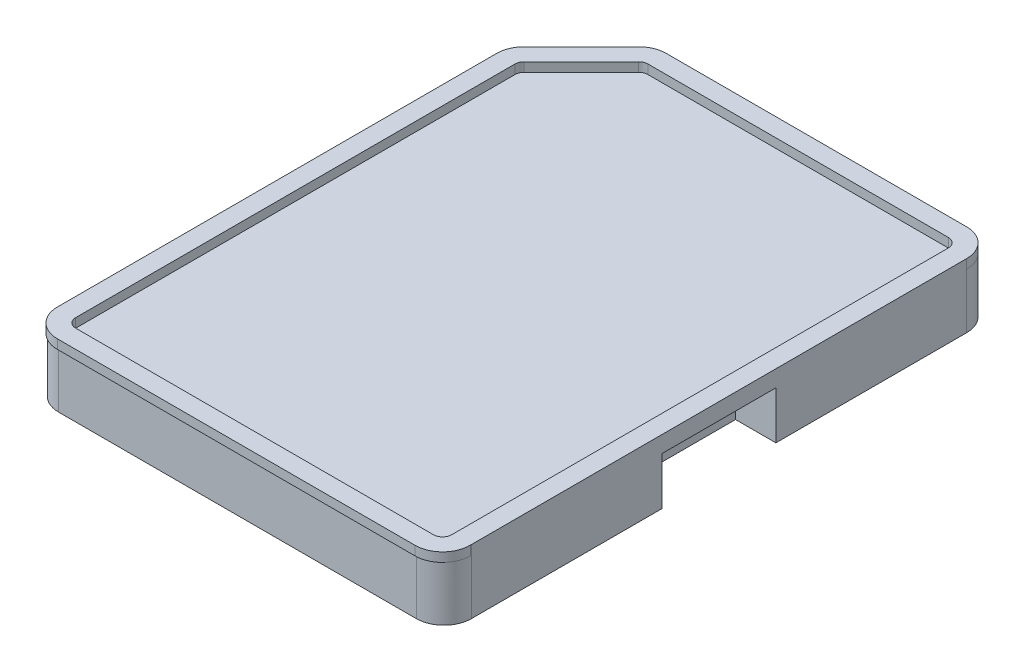
SolidWorks part; units mm, degrees
ref_plane "Спереди" through (0, 0, 0) normal (0, 0, 1) x (1, 0, 0)
ref_plane "Сверху" through (0, 0, 0) normal (0, 1, 0) x (1, 0, 0)
ref_plane "Справа" through (0, 0, 0) normal (1, 0, 0) x (0, 0, -1)
sketch "surface_sketch" plane through (0, 0, 0) normal (0, 1, 0) x (1, 0, 0)
  line L2 (-12.4, -15) -> (10.1, -15)
  line L3 (10.1, -15) -> (10.1, 15)
  line L4 (0.1, 0) -> (0.1, -15) construction
  line L5 (0.1, 0) -> (10.1, 0) construction
  line L7 (-8.4, 15) -> (10.1, 15)
  line L8 (-12.4, 11) -> (-12.4, -15)
  line L9 (-3.65, -15) -> (-3.65, -7.5) construction
  line L10 (-3.65, -7.5) -> (0.1, -7.5) construction
  line L11 (-3.65, -7.5) -> (-3.65, 0) construction
  line L12 (-3.65, 0) -> (-3.65, 7.5) construction
  line L13 (-1.3, 7.5) -> (-6, 7.5)
  line L14 (-6, 0) -> (-1.3, 0)
  line L15 (-6, -7.5) -> (-1.3, -7.5)
  line L16 (6.2, -7.5) -> (1.5, -7.5)
  line L17 (6.2, 0) -> (1.5, 0) construction
  line L18 (3.85, 7.5) -> (1.5, 7.5)
  line L19 (0, 0) -> (0.1, 0) construction
  line L20 (3.85, 7.5) -> (6.2, 7.5)
  line L21 (-8.4, 15) -> (-12.4, 11)
  line L22 (-12.4, 11) -> (-12.4, 15) construction
  line L23 (-12.4, 15) -> (-8.4, 15) construction
  circle A0 centre (-3.65, 7.5) radius 2.35
  circle A1 centre (-3.65, 0) radius 2.35
  circle A2 centre (-3.65, -7.5) radius 2.35
  circle A3 centre (3.85, -7.5) radius 2.35
  circle A4 centre (3.85, 0) radius 2.35
  circle A5 centre (3.85, 7.5) radius 2.35
  dimension "D9" = 4.7
  dimension "D10" = 4.7
  dimension "D11" = 4.7
  dimension "D1" = 22.5
  dimension "D2" = 30
  dimension "D5" = 7.5
  dimension "D6" = 3.75
  dimension "D7" = 7.5
  dimension "D8" = 7.5
  dimension "D3" = 10
  dimension "D4" = 0.1
  dimension "D12" = 4
  dimension "D13" = 4
extrude "body" add sketch "surface_sketch" against normal blind 3
ref_plane "midplane" through (-1.15, 0, 0) normal (1, 0, 0) x (0, 0, -1)
sketch "magnet_cutout_sketch" plane through (0, -3, 0) normal (0, -1, 0) x (1, 0, 0)
  line L0 (10.1, 15) -> (10.1, -15) construction
  line L1 (7.9, 3.1) -> (10.1, 3.1)
  line L2 (7.9, 3.1) -> (7.9, -3.1)
  line L3 (7.9, -3.1) -> (10.1, -3.1)
  line L4 (10.1, 3.1) -> (10.1, -3.1)
  line L5 (9, -3.1) -> (9, 3.1) construction
  line L6 (7.9, 0) -> (10.1, 0) construction
  line L7 (-1.15, 15) -> (-1.15, -15) construction
  line L8 (-12.4, 15) -> (10.1, 15) construction
  line L9 (-8.4, -15) -> (10.1, -15) construction
  line L11 (-1.15, 0) -> (10.1, 0) construction
  line L12 (10.1, 15) -> (10.1, -15) construction
  point P0 (9, 0)
  dimension "D1" = 2.2
  dimension "D2" = 6.2
extrude "magnet_cutout" cut sketch "magnet_cutout_sketch" against normal blind 2.6
mirror "magnet_cutout_mirror" about plane through (-1.15, 0, 0) normal (1, 0, 0) of "magnet_cutout"
sketch "border_sketch" plane through (0, 0, 0) normal (0, 1, 0) x (1, 0, 0)
  line L0 (-12.4, -13.5714) -> (-12.4, 10.3787)
  line L1 (10.1, -13.5714) -> (10.1, 13.5)
  line L2 (8.6, 15) -> (-7.7787, 15)
  line L4 (-1.15, 15) -> (-1.15, -15.0714) construction
  line L5 (-12.4, -0.0357) -> (10.1, -0.0357) construction
  line L6 (-8.4, 15) -> (10.1, 15) construction
  line L7 (10.1, -15) -> (10.1, 15) construction
  line L8 (-10.9, -15.0714) -> (8.6, -15.0714)
  line L9 (-8.8393, 14.5607) -> (-11.9607, 11.4393)
  arc A2 (10.1, 13.5) -> (8.6, 15) centre (8.6, 13.5) ccw
  arc A4 (10.1, -13.5714) -> (8.6, -15.0714) centre (8.6, -13.5714) cw
  arc A5 (-12.4, -13.5714) -> (-10.9, -15.0714) centre (-10.9, -13.5714) ccw
  arc A6 (-12.4, 10.3787) -> (-11.9607, 11.4393) centre (-10.9, 10.3787) cw
  arc A7 (-8.8393, 14.5607) -> (-7.7787, 15) centre (-7.7787, 13.5) cw
  point P6 (10.1, -15.0714)
  point P19 (-12.4, 11)
  point P27 (-8.4, 15)
  dimension "D1" = 1.5
  dimension "D2" = 1.5
extrude "border" add sketch "border_sketch" along normal blind 0.5 thin contours L0 L2 A2 L1
fillet "Скругление1" radius 1.5 5 edges at (10.1, -1.5, 15) (10.1, -1.5, -15) (-12.4, -1.5, 15) (-8.4, -1.5, -15) (-12.4, -1.5, -11)
equation "\"hole_diam\"= 4.7мм"
equation "\"cell_width\"= \"cell_pace\""
equation "\"cell_pace\"= 22.5мм'distance between neighbouring cells"
equation "\"holes_horisontal_dist\"= 7.5"
equation "\"holes_vertical_dist\"= \"holes_horisontal_dist\""
equation "\"cell_length\"= \"holes_vertical_dist\" * 4"
equation "\"char_width\"= 15"
equation "\"char_thickness\"= 2.5"
equation "\"char_height\"= 22"
equation "\"D1@body\" = \"cell_surface_height\""
equation "\"char_champfer_width\"= 1"
equation "\"char_depth\"= 1.5"
equation "\"D1@Эскиз19\"=\"cell_width\""
equation "\"D2@surface_sketch\"=\"cell_length\""
equation "\"D9@surface_sketch\"=\"hole_diam\""
equation "\"D8@surface_sketch\"=\"holes_vertical_dist\""
equation "\"D6@surface_sketch\"=\"holes_horisontal_dist\"/2"
equation "\"D1@surface_sketch\"=\"cell_width\""
equation "\"D5@surface_sketch\"=\"holes_vertical_dist\""
equation "\"D7@surface_sketch\"=\"holes_vertical_dist\""
equation "\"magnet_cut_height\"= 2.6"
equation "\"magnet_cut_width\"= 6.2"
equation "\"magnet_cut_depth\"= 2.2"
equation "\"D1@magnet_cutout_sketch\" = \"magnet_cut_depth\""
equation "\"D2@magnet_cutout_sketch\" = \"magnet_cut_width\""
equation "\"D1@magnet_cutout\" = \"magnet_cut_height\""
equation "\"border_width\"= 1"
equation "\"border_height\"= 0.5"
equation "\"D1\"= \"border_height\""
equation "\"D5@border\" = \"border_width\""
equation "\"D2@back_complementary_holes_sketch\" = \"hole_diam\" - 0.2"
equation "\"D3@back_complementary_holes_sketch\" = \"holes_vertical_dist\""
equation "\"D4@back_complementary_holes_sketch\" = \"holes_horisontal_dist\" / 2"
equation "\"D5@back_complementary_holes_sketch\" = \"holes_vertical_dist\""
equation "\"D6@back_complementary_holes_sketch\" = \"holes_vertical_dist\""
equation "\"D7@back_complementary_holes_sketch\" = \"hole_diam\" - 0.2"
equation "\"D8@back_complementary_holes_sketch\" = \"hole_diam\" - 0.2"
